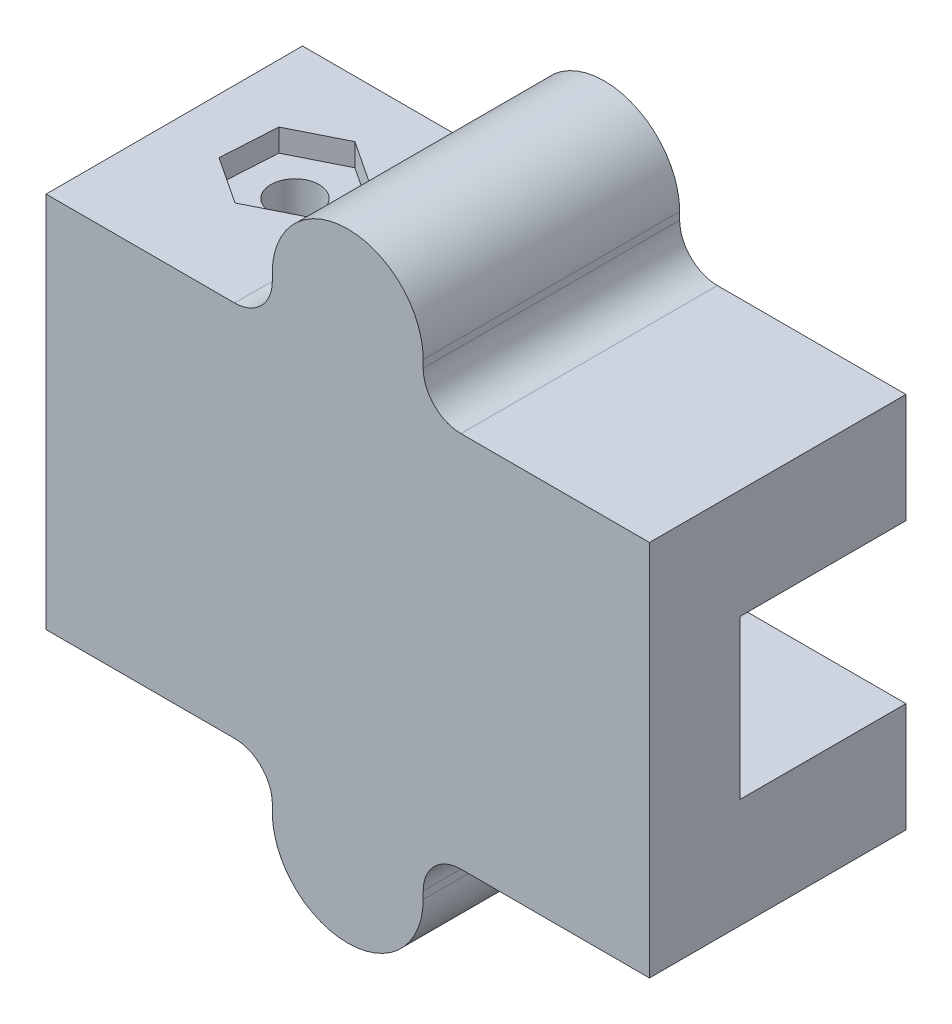
SolidWorks part; units mm, degrees
material "ABS"
ref_plane "Front Plane" through (0, 0, 0) normal (0, 0, 1) x (1, 0, 0)
ref_plane "Top Plane" through (0, 0, 0) normal (0, 1, 0) x (1, 0, 0)
ref_plane "Right Plane" through (0, 0, 0) normal (1, 0, 0) x (0, 0, -1)
sketch "Sketch1" plane through (0, 0, 0) normal (0, 0, 1) x (1, 0, 0)
  line L1 (0, 5.25) -> (0, -5.25) construction
  line L4 (-20, 12.5) -> (-7.5, 12.5)
  line L5 (20, -12.5) -> (20, 12.5)
  line L6 (-20, -12.5) -> (-7.5, -12.5)
  line L7 (-20, -12.5) -> (-20, 12.5)
  line L8 (-20, -5.25) -> (20, -5.25)
  line L9 (-20, -5.25) -> (20, -5.25) construction
  line L10 (-20, 5.25) -> (20, 5.25)
  line L11 (-20, 5.25) -> (20, 5.25) construction
  line L12 (-5, 15.5) -> (-5, 15)
  line L13 (5, 15.5) -> (5, 15)
  line L14 (7.5, 12.5) -> (20, 12.5)
  line L15 (-20, 12.5) -> (20, 12.5) construction
  line L17 (-20, 0) -> (20, 0) construction
  line L18 (7.5, -12.5) -> (20, -12.5)
  line L19 (-20, -12.5) -> (20, -12.5) construction
  line L20 (-5, -15) -> (-5, -15.5)
  line L21 (5, -15) -> (5, -15.5)
  circle A0 centre (0, 15.5) radius 2.4
  arc A1 (5, 15.5) -> (-5, 15.5) centre (0, 15.5) ccw
  arc A2 (5, 15) -> (7.5, 12.5) centre (7.5, 15) ccw
  arc A3 (-5, 15) -> (-7.5, 12.5) centre (-7.5, 15) cw
  arc A4 (5, -15) -> (7.5, -12.5) centre (7.5, -15) cw
  arc A5 (-5, -15) -> (-7.5, -12.5) centre (-7.5, -15) ccw
  circle A6 centre (0, -15.5) radius 2.4
  arc A7 (5, -15.5) -> (-5, -15.5) centre (0, -15.5) cw
  point P3 (0, 0)
  point P15 (5, 12.5)
  point P22 (-5, 12.5)
  dimension "D1" = 10.5
  dimension "D2" = 2.5
  dimension "D3" = 4.8
  dimension "D4" = 25
  dimension "D5" = 40
extrude "Boss-Extrude1" add sketch "Sketch1" along normal blind 11 contours L12 A3 L4 L7 L10 L5 L14 A2 L13 A1 A0 | A7 L21 A4 L18 L5 L8 L7 L6 A5 L20 A6 | A6 | A0 region at (0, 10.0051, 0) region at (0, -10.0051, 0) region at (0, 15.5, 0) region at (0, -15.5, 0)
extrude "Boss-Extrude2" add sketch "Sketch1<3>" along normal blind 6 from surface contours L12 A3 L4 L7 L10 L5 L14 A2 L13 A1 A0 | A6 | A7 L21 A4 L18 L5 L8 L7 L6 A5 L20 A6 | A0 | L10 L7 L8 L5 region at (0, 10.0051, 0) region at (0, 0, 0) region at (0, -10.0051, 0) region at (0, 15.5, 0) region at (0, -15.5, 0) starting at face at (0, 12.5464, 11)
sketch "Sketch1<3>" plane through (0, 0, 0) normal (0, 0, 1) x (1, 0, 0) same geometry as "Sketch1"
sketch "Sketch3" plane through (0, 0, 11) normal (0, 0, -1) x (-1, 0, 0)
  line L0 (-20, 0) -> (-14, 0) construction
  line L3 (-20, 5.25) -> (-20, -5.25) construction
  circle A0 centre (-14, 0) radius 4.25
  point P2 (0, 0)
  point P3 (-20, 0)
  point P6 (-20, 0)
  dimension "D1" = 8.5
  dimension "D2" = 6
extrude "Cut-Extrude1" cut sketch "Sketch3" against normal blind 5
sketch "Sketch4" plane through (0, -12.5, 0) normal (0, -1, 0) x (1, 0, 0)
  line L1 (-20, 17) -> (-20, 0) construction
  circle A0 centre (-13, 7.5) radius 1.6
  dimension "D1" = 3.2
  dimension "D2" = 7.5
  dimension "D3" = 7
extrude "Cut-Extrude2" cut sketch "Sketch4" against normal through all
sketch "Sketch5" plane through (0, 12.5, 0) normal (0, 1, 0) x (1, 0, 0)
  line L1 (-9.868, -9.5674) -> (-9.6436, -5.8213)
  line L2 (-9.6436, -5.8213) -> (-12.7756, -3.7539)
  line L3 (-12.7756, -3.7539) -> (-16.132, -5.4326)
  line L4 (-16.132, -5.4326) -> (-16.3564, -9.1787)
  line L5 (-16.3564, -9.1787) -> (-13.2244, -11.2461)
  line L6 (-13.2244, -11.2461) -> (-9.868, -9.5674)
  circle A0 centre (-13, -7.5) radius 3.25 construction
  dimension "D1" = 6.5
extrude "Cut-Extrude3" cut sketch "Sketch5" against normal blind 1.5
sketch "Sketch7" plane through (0, 0, 0) normal (0, 0, -1) x (-1, 0, 0)
  line L5 (-20, 0) -> (20, 0) construction
  line L18 (-5, 8.875) -> (5, 8.875) construction
  line L19 (-5, 11.475) -> (5, 11.475)
  line L20 (-5, 6.275) -> (5, 6.275)
  line L21 (-5, -8.875) -> (5, -8.875) construction
  line L22 (-5, -11.475) -> (5, -11.475)
  line L23 (-5, -6.275) -> (5, -6.275)
  line L24 (-20, 5.25) -> (-20, -5.25) construction
  line L25 (20, 5.25) -> (20, -5.25) construction
  arc A0 (-5, 11.475) -> (-5, 6.275) centre (-5, 8.875) ccw
  arc A1 (5, 6.275) -> (5, 11.475) centre (5, 8.875) ccw
  arc A2 (-5, -11.475) -> (-5, -6.275) centre (-5, -8.875) cw
  arc A3 (5, -6.275) -> (5, -11.475) centre (5, -8.875) cw
  point P2 (-20, 0)
  point P5 (20, 0)
  point P8 (0, 8.875)
  point P15 (0, -8.875)
  dimension "D1" = 5.2
extrude "Cut-Extrude5" cut sketch "Sketch7" against normal blind 5.2
sketch "Sketch9" plane through (0, 0, 0) normal (0, 0, -1) x (-1, 0, 0)
  line L0 (20, 0) -> (-20, 0) construction
  line L1 (20, 5.25) -> (20, -5.25) construction
  line L2 (-20, 5.25) -> (-20, -5.25) construction
  circle A0 centre (0, -15.5) radius 2.4
  circle A1 centre (0, 15.5) radius 2.4
  dimension "D1" = 4.8
extrude "Cut-Extrude6" cut sketch "Sketch9" against normal blind 6
